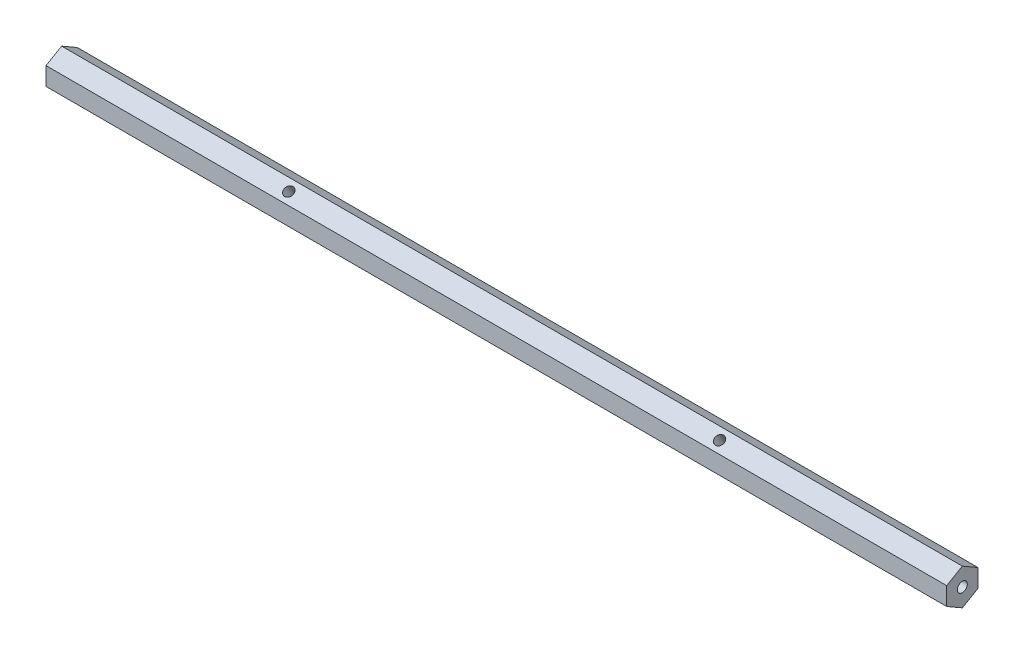
SolidWorks part; units mm, degrees
material "6061-T6 (SS)"
ref_plane "Front" through (0, 0, 0) normal (0, 0, 1) x (1, 0, 0)
ref_plane "Top" through (0, 0, 0) normal (0, 1, 0) x (1, 0, 0)
ref_plane "Right" through (0, 0, 0) normal (1, 0, 0) x (0, 0, -1)
ref_axis "Axis1" through (-80.9, 0, 0) along (1, 0, 0)
sketch "Sketch1" plane through (0, 0, 0) normal (1, 0, 0) x (0, 0, -1)
  line L1 (0, 7.3323) -> (-6.35, 3.6662)
  line L2 (-6.35, 3.6662) -> (-6.35, -3.6662)
  line L3 (-6.35, -3.6662) -> (0, -7.3323)
  line L4 (0, -7.3323) -> (6.35, -3.6662)
  line L5 (6.35, -3.6662) -> (6.35, 3.6662)
  line L6 (6.35, 3.6662) -> (0, 7.3323)
  circle A0 centre (0, 0) radius 6.35 construction
  dimension "D1" = 12.7
extrude "Boss-Extrude1" add sketch "Sketch1" along normal up to surface (365.125 mm away)
hole_wizard "#10-32 Tapped Hole1" positions "Sketch2" profile "Sketch3" tap size "#10-32" standard "ANSI Inch"
sketch "Sketch2" plane through (365.125, 0, 0) normal (1, 0, 0) x (0, 0, -1)
  point P0 (0, 0)
sketch "Sketch3" plane through (365.125, 0, 0) normal (0, 1, 0) x (0, 0, -1)
  line L0 (0, 0) -> (0, 13.2529)
  line L1 (0, 13.2529) -> (2.0193, 12.0396)
  line L2 (2.0193, 12.0396) -> (2.0193, 0)
  line L5 (2.0193, 0) -> (0, 0)
  line L10 (0, 13.2529) -> (-2.0193, 12.0396) construction
  line L11 (0, -6.35) -> (0, 107.95) construction
  dimension "Tap Drill Dia." = 4.0386
  dimension "Tap Drill Depth" = 12.0396
  dimension "Drill Angle" = 118
cosmetic thread "Hole Thread1" parameters "D1"=9.652, "D2"=4.826
hole_wizard "#10-32 Tapped Hole2" positions "Sketch4" profile "Sketch5" tap size "#10-32" standard "ANSI Inch"
sketch "Sketch4" plane through (0, 0, 0) normal (-1, 0, 0) x (0, 0, 1)
  point P0 (0, 0)
sketch "Sketch5" plane through (0, 0, 0) normal (0, 1, 0) x (0, 0, 1)
  line L0 (0, 0) -> (0, 13.2529)
  line L1 (0, 13.2529) -> (2.0193, 12.0396)
  line L2 (2.0193, 12.0396) -> (2.0193, 0)
  line L5 (2.0193, 0) -> (0, 0)
  line L10 (0, 13.2529) -> (-2.0193, 12.0396) construction
  line L11 (0, -6.35) -> (0, 107.95) construction
  dimension "Tap Drill Dia." = 4.0386
  dimension "Tap Drill Depth" = 12.0396
  dimension "Drill Angle" = 118
cosmetic thread "Hole Thread2" parameters "D1"=9.652, "D2"=4.826
sketch "Sketch6" plane through (0, 5.4993, 3.175) normal (0, 0.866, 0.5) x (1, 0, 0)
  line L0 (0, 7.3323) -> (0, 3.6662) construction
  line L3 (0, 0) -> (95.25, 0) construction
  line L4 (0, 3.6662) -> (0, -3.6662) construction
  line L9 (269.875, 0) -> (365.125, 0) construction
  line L10 (365.125, -3.6662) -> (365.125, 3.6662) construction
  circle A0 centre (95.25, 0) radius 1.905
  circle A1 centre (269.875, 0) radius 1.905
  dimension "D1" = 3.81
  dimension "D2" = 95.25
extrude "Cut-Extrude1" cut sketch "Sketch6" against normal through all
